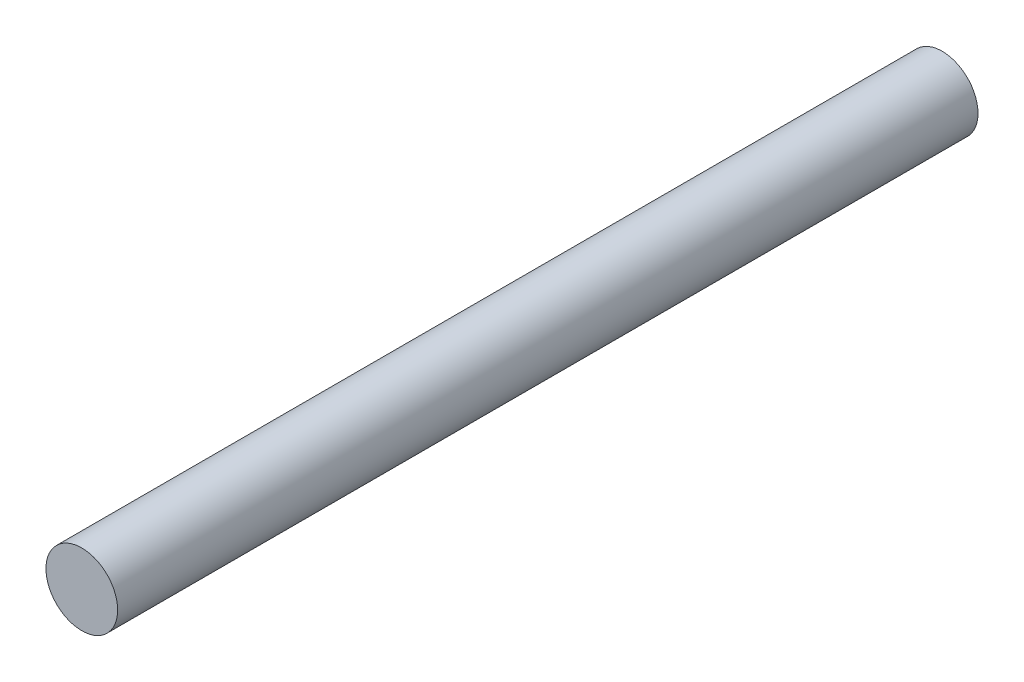
SolidWorks part; units mm, degrees
material "A286 铁基超合金"
ref_plane "前视基准面" through (0, 0, 0) normal (0, 0, 1) x (1, 0, 0)
ref_plane "上视基准面" through (0, 0, 0) normal (0, 1, 0) x (1, 0, 0)
ref_plane "右视基准面" through (0, 0, 0) normal (1, 0, 0) x (0, 0, -1)
sketch "草图3" plane through (0, 0, 0) normal (0, 0, 1) x (1, 0, 0)
  circle A0 centre (0, 0) radius 5
  dimension "D1" = 10
extrude "凸台-拉伸1" add sketch "草图3" along normal mid plane 120
